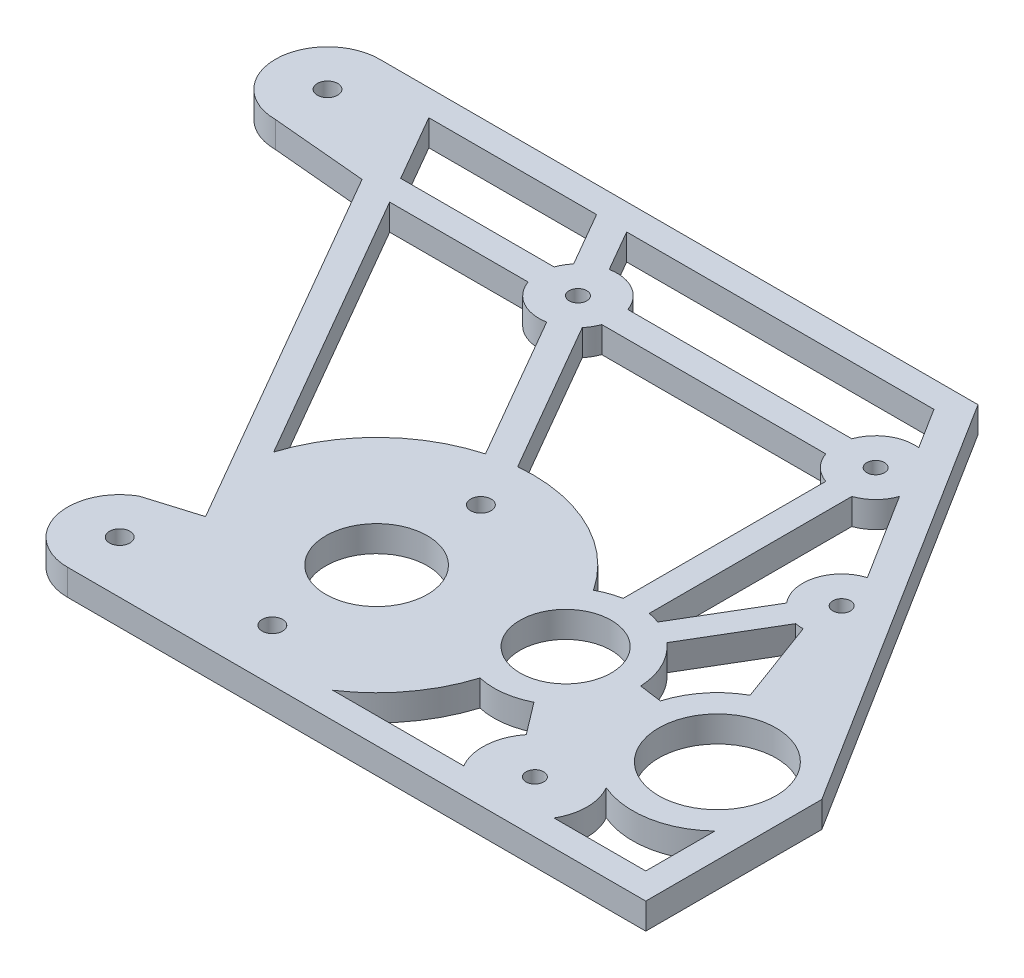
SolidWorks part; units mm, degrees
ref_plane "Front Plane" through (0, 0, 0) normal (0, 0, 1) x (1, 0, 0)
ref_plane "Top Plane" through (0, 0, 0) normal (0, 1, 0) x (1, 0, 0)
ref_plane "Right Plane" through (0, 0, 0) normal (1, 0, 0) x (0, 0, -1)
sketch "Sketch1" plane through (0, 0, 0) normal (0, 1, 0) x (1, 0, 0)
  line L0 (-190.7858, 72.591) -> (-106.965, -72.591)
  line L1 (-190.7858, 72.591) -> (190.7858, 72.591)
  line L2 (-190.7858, 72.591) -> (-190.7858, -72.591)
  line L3 (-190.7858, -72.591) -> (190.7858, -72.591)
  line L4 (190.7858, 72.591) -> (190.7858, -72.591)
  line L5 (-190.7858, 72.591) -> (190.7858, -72.591) construction
  line L6 (-190.7858, -72.591) -> (190.7858, 72.591) construction
  line L7 (-161.4564, 72.591) -> (-77.6356, -72.591)
  line L8 (-176.1211, 72.591) -> (-92.3003, -72.591) construction
  line L9 (-62.4429, -34.491) -> (-22.2218, -28.6714) construction
  line L10 (-22.2218, -28.6714) -> (20.5643, -34.491) construction
  line L11 (20.5643, -34.491) -> (-62.4429, -34.491) construction
  line L12 (47.5645, 72.591) -> (47.5645, -72.591)
  line L13 (-168.7887, 47.191) -> (-145.5814, 45.0947)
  line L14 (-105.9826, -48.8924) -> (-93.5106, -45.0947)
  circle A0 centre (-62.4429, -34.491) radius 32.2072
  circle A1 centre (-62.4429, -34.491) radius 12.3825
  circle A2 centre (-62.4429, -9.091) radius 2.4892
  circle A3 centre (-62.4429, -59.891) radius 2.4892
  circle A4 centre (-22.2218, -28.6714) radius 11.1252
  circle A5 centre (20.5643, -34.491) radius 14.3002
  circle A6 centre (-168.7887, 59.891) radius 2.4892
  circle A7 centre (-99.6326, -59.891) radius 2.4892
  circle A8 centre (-168.7887, 59.891) radius 12.7
  circle A9 centre (-99.6326, -59.891) radius 12.7
  point P0 (0, 0)
  dimension "D2" = 120
  dimension "D5" = 64.4144
  dimension "D6" = 24.765
  dimension "D7" = 4.9784
  dimension "D8" = 4.9784
  dimension "D9" = 50.8
  dimension "D10" = 25.4
  dimension "D11" = 12.7
  dimension "D15" = 22.2504
  dimension "D16" = 28.6004
  dimension "D18" = 4.9784
  dimension "D19" = 4.9784
  dimension "D20" = 12.7
  dimension "D21" = 12.7
  dimension "D22" = 25.4
  dimension "D23" = 31.75
  dimension "D1" = 145.1819
  dimension "D3" = 25.4
  dimension "D4" = 12.7
  dimension "D12" = 40.64
  dimension "D13" = 43.18
  dimension "D14" = 83.0072
  dimension "D17" = 27.0002
  dimension "D24" = 31.75
  dimension "D25" = 125.161
  dimension "D26" = 23.3018
extrude "Boss-Extrude1" add sketch "Sketch1" along normal blind 6.35 contours A4 A0 L7 L3 L12 L1 A5 | A4 A0 A3 A2 A1 | A9 L14 A7 | A9 L7 L14 | A9 L3 L7 | A8 A6 | A8 L13 L7 | A8 L7 L1 region at (-179.4762, 0, -66.0614) region at (-162.2256, 0, -71.2586) region at (-111.5529, 0, 56.6969) region at (-154.6803, 0, -50.934) region at (-75.6062, 0, 6.0972) region at (-35.8851, 0, -14.6154) region at (-85.7245, 0, 67.9208) region at (-94.2255, 0, 47.5186)
sketch "Sketch2" plane through (0, 6.35, 0) normal (0, 1, 0) x (1, 0, 0)
  line L0 (-145.5814, 45.0947) -> (-93.5106, -45.0947)
  line L1 (-154.124, 72.591) -> (-70.3032, -72.591)
  line L2 (-168.7887, 72.591) -> (47.5645, 72.591) construction
  line L3 (-99.6326, -72.591) -> (47.5645, -72.591) construction
  line L4 (-150.4579, 66.241) -> (47.5645, 66.241)
  line L5 (47.5645, 72.591) -> (47.5645, -72.591) construction
  line L6 (41.2145, 72.591) -> (41.2145, -72.591)
  line L7 (-73.9694, -66.241) -> (41.2145, -66.241)
  line L8 (-62.4429, -9.091) -> (-105.9359, 66.241) construction
  line L9 (-22.2218, -28.6714) -> (-22.2218, 66.241) construction
  line L10 (20.5643, -34.491) -> (20.5643, -66.241) construction
  line L11 (-22.2218, -28.6714) -> (1.5143, -59.891) construction
  line L12 (-22.2218, -28.6714) -> (20.5643, -34.491) construction
  line L13 (-139.2615, 46.8482) -> (41.2145, 46.8482) construction
  line L14 (-141.0946, 50.0232) -> (41.2145, 50.0232)
  line L15 (-137.4284, 43.6732) -> (41.2145, 43.6732)
  line L16 (-109.602, 66.241) -> (-72.6391, 2.2194)
  line L17 (-102.2697, 66.241) -> (-66.0124, 3.4415)
  line L18 (-25.3968, 66.241) -> (-25.3968, -11.487)
  line L19 (-19.0468, 66.241) -> (-19.0468, -11.487)
  line L20 (-4.7663, -27.8414) -> (0.7737, -28.5949)
  line L21 (-5.6221, -34.1334) -> (-0.0821, -34.887)
  line L22 (34.8645, 72.591) -> (34.8645, -72.591)
  line L23 (-14.3487, -44.2726) -> (-8.4556, -52.0238)
  line L24 (-9.2938, -40.4294) -> (-3.4006, -48.1806)
  line L25 (-19.0468, 66.241) -> (34.8645, -19.5935)
  line L26 (-27.416, 66.241) -> (22.9704, -13.9814)
  line L27 (-13.2415, 43.6732) -> (22.9704, -13.9814) construction
  line L28 (4.8645, 14.8459) -> (-19.0468, -0.1724) construction
  line L29 (-19.0468, 66.241) -> (-23.0351, 72.591)
  line L30 (-27.416, 66.241) -> (-31.4043, 72.591)
  line L31 (34.8645, -19.5935) -> (47.5645, -39.8137)
  line L32 (2.8001, 13.5493) -> (-22.2218, -28.6714) construction
  line L33 (2.8001, 13.5493) -> (20.5643, -34.491) construction
  line L34 (-4.5097, 7.4426) -> (-16.192, -12.2694)
  line L35 (0.953, 4.2051) -> (-10.7292, -15.5069)
  line L36 (2.9367, 4.0253) -> (10.5095, -16.454)
  line L37 (8.8926, 6.2276) -> (16.4653, -14.2517)
  circle A0 centre (-62.4429, -34.491) radius 38.1
  circle A1 centre (-22.2218, -28.6714) radius 17.4752
  circle A2 centre (20.5643, -34.491) radius 20.6502
  circle A3 centre (1.5143, -59.891) radius 2.1527
  circle A4 centre (1.5143, -59.891) radius 12.7
  circle A5 centre (-94.7395, 46.8482) radius 2.1527
  circle A6 centre (-94.7395, 46.8482) radius 9.525
  circle A7 centre (-22.2218, 46.8482) radius 2.1527
  circle A8 centre (-22.2218, 46.8482) radius 9.525
  circle A9 centre (2.8001, 13.5493) radius 9.525
  circle A10 centre (2.8001, 13.5493) radius 2.1527
  point P68 (-13.2415, 43.6732)
  line M27 (-99.6326, -72.591) -> (47.5645, -72.591)
  line M28 (47.5645, -72.591) -> (47.5645, 72.591)
  line M29 (47.5645, 72.591) -> (-168.7887, 72.591)
  dimension "D5" = 34.9504
  dimension "D6" = 41.3004
  dimension "D7" = 4.3053
  dimension "D9" = 25.4
  dimension "D11" = 4.3053
  dimension "D12" = 19.05
  dimension "D13" = 4.3053
  dimension "D14" = 19.05
  dimension "D21" = 19.05
  dimension "D22" = 4.3053
  dimension "D1" = 6.35
  dimension "D2" = 6.35
  dimension "D3" = 6.35
  dimension "D4" = 6.35
  dimension "D8" = 19.05
  dimension "D10" = 1.7536
  dimension "D15" = 6.35
  dimension "D16" = 6.35
  dimension "D17" = 6.35
  dimension "D18" = 6.35
  dimension "D19" = 12.7
  dimension "D20" = 6.35
  dimension "D23" = 6.35
  dimension "D24" = 6.35
extrude "Cut-Extrude2" cut sketch "Sketch2" against normal through all contours L6 L31 L4 M28 | L6 L4 M29 M28 | L4 L22 L14 L6 | L22 L4 L6 M29 | L29 L4 L22 M29 | L4 L25 L14 L22 | L14 L25 L15 L22 | L14 L22 L15 L6 | L15 L25 L22 | A2 L31 L6 L15 L22 | L31 L6 M27 M28 | A4 L7 L22 A2 | A4 L23 A1 A0 L7 | A9 L35 A1 L20 A2 L36 | A9 L26 A8 L19 A1 L34 | A8 L15 A6 L17 A0 A1 L18 | A8 L18 L26 L4 L17 A6 L14 | A6 L16 L4 L1 L14 | A6 L15 L1 A0 L16 | A5 | A7 | A8 L26 L18 | A10 | A3 | L31 A2 region at (-125.5477, 6.35, -58.1926) region at (-61.2079, 6.35, -58.6096) region at (6.8999, 6.35, -69.4537) region at (-103.6381, 6.35, -17.0075) region at (-24.0244, 6.35, -58.4944) region at (10.3668, 6.35, -58.4141) region at (38.0395, 6.35, -69.416) region at (38.0395, 6.35, -58.1321) region at (13.9831, 6.35, -46.8988) region at (44.3895, 6.35, -69.416) region at (44.4424, 6.35, -15.699) region at (38.0395, 6.35, -46.8482) region at (21.6189, 6.35, -22.5843) region at (-21.5834, 6.35, 57.1732) region at (-50.2878, 6.35, -22.0192) region at (38.1214, 6.35, -9.7689) region at (-12.5353, 6.35, -16.8952) region at (44.248, 6.35, 53.5622) region at (37.7382, 6.35, 23.7043) region at (24.8714, 6.35, 59.9323) region at (0.0693, 6.35, 13.136) region at (1.5143, 6.35, 59.891) region at (-94.7395, 6.35, -46.8482) region at (-22.2218, 6.35, -46.8482) region at (2.8001, 6.35, -13.5493)
fillet "Fillet1" [suppressed] radius 2.54
